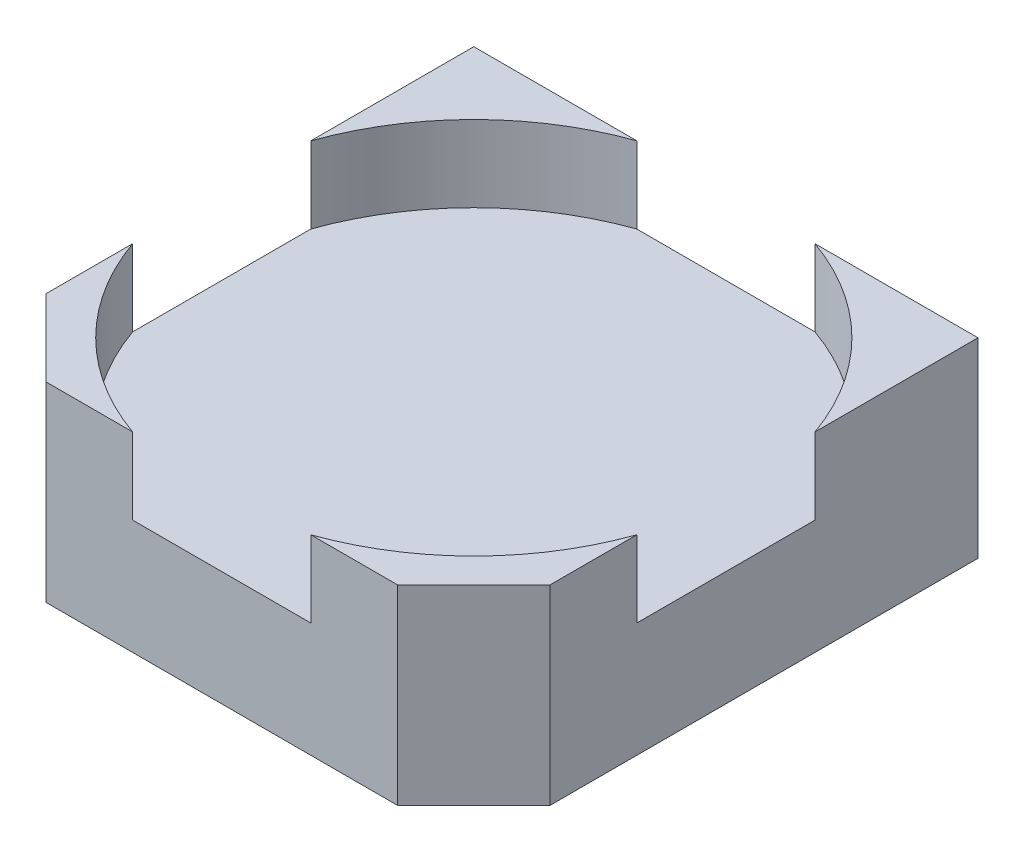
SolidWorks part; units mm, degrees
ref_plane "Front Plane" through (0, 0, 0) normal (0, 0, 1) x (1, 0, 0)
ref_plane "Top Plane" through (0, 0, 0) normal (0, 1, 0) x (1, 0, 0)
ref_plane "Right Plane" through (0, 0, 0) normal (1, 0, 0) x (0, 0, -1)
sketch "Sketch1" plane through (0, 0, 0) normal (0, 1, 0) x (1, 0, 0)
  line L1 (-3.3, -3.3) -> (3.3, -3.3)
  line L2 (-3.3, -3.3) -> (-3.3, 3.3)
  line L3 (-3.3, 3.3) -> (3.3, 3.3)
  line L4 (3.3, -3.3) -> (3.3, 3.3)
  line L5 (-3.3, -3.3) -> (3.3, 3.3) construction
  line L6 (-3.3, 3.3) -> (3.3, -3.3) construction
  point P0 (0, 0)
  dimension "D1" = 6.6
  dimension "D2" = 6.6
extrude "Boss-Extrude1" add sketch "Sketch1" along normal blind 2.5
chamfer "Chamfer1" distance 1 angle 45 2 edges at (3.3, 1.25, 3.3) (-3.3, 1.25, 3.3)
sketch "Sketch3" plane through (0, 2.5, 0) normal (0, 1, 0) x (1, 0, 0)
  circle A0 centre (0, 0) radius 3.5
  dimension "D1" = 7
extrude "Cut-Extrude1" cut sketch "Sketch3" against normal blind 1
sketch "Sketch4" plane through (0, 0, 0) normal (0, -1, 0) x (1, 0, 0)
  line L0 (0, -1.375) -> (0, 1.375) construction
  line L1 (0.45, -3.3) -> (-0.45, -3.3)
  line L2 (0.45, -3.3) -> (0.45, -1.1)
  line L4 (-0.45, -3.3) -> (-0.45, -1.1)
  line L5 (3.3, -3.3) -> (-3.3, -3.3) construction
  arc A0 (0.45, -1.1) -> (-0.45, -1.1) centre (0, -1.1) ccw
  point P4 (0, -3.3)
  dimension "D1" = 0.9
ref_axis "Axis2" through (-3.3, 0, -3.3) along (1, 0, 0)
ref_plane "Plane3" through (0, 0.2, 0) normal (0, -1, 0) x (-1, 0, 0)
ref_axis "Axis3" through (-3.63, 0.2, 0) along (1, 0, 0)
ref_plane "Plane4" through (0, 0.1993, -0.0121) normal (0, 0.9982, -0.0605) x (1, 0, 0)
sketch "Sketch6" plane through (0, 0.1993, -0.0121) normal (0, 0.9982, -0.0605) x (1, 0, 0)
  line L0 (-0.45, 3.294) -> (-0.45, 1.098) construction
  line L1 (0.45, 3.294) -> (0.45, 1.098) construction
  line L2 (0.45, 3.294) -> (-0.45, 3.294) construction
  line L3 (-0.45, 3.294) -> (-0.45, 1.098)
  line L4 (0.45, 3.294) -> (0.45, 1.098)
  line L5 (0.45, 3.294) -> (-0.45, 3.294)
  ellipse E0 centre (0, 1.098) end of major axis (0.45, 1.098) minor radius 0.4492 (-0.45, 1.098) -> (0.45, 1.098) ccw construction
  ellipse E1 centre (0, 1.098) end of major axis (0.45, 1.098) minor radius 0.4492 (-0.45, 1.098) -> (0.45, 1.098) ccw
extrude "Cut-Extrude3" cut sketch "Sketch6" against normal through all
mirror "Mirror1" about plane through (0, 0, 0) normal (0, 0, 1) of "Cut-Extrude3"
